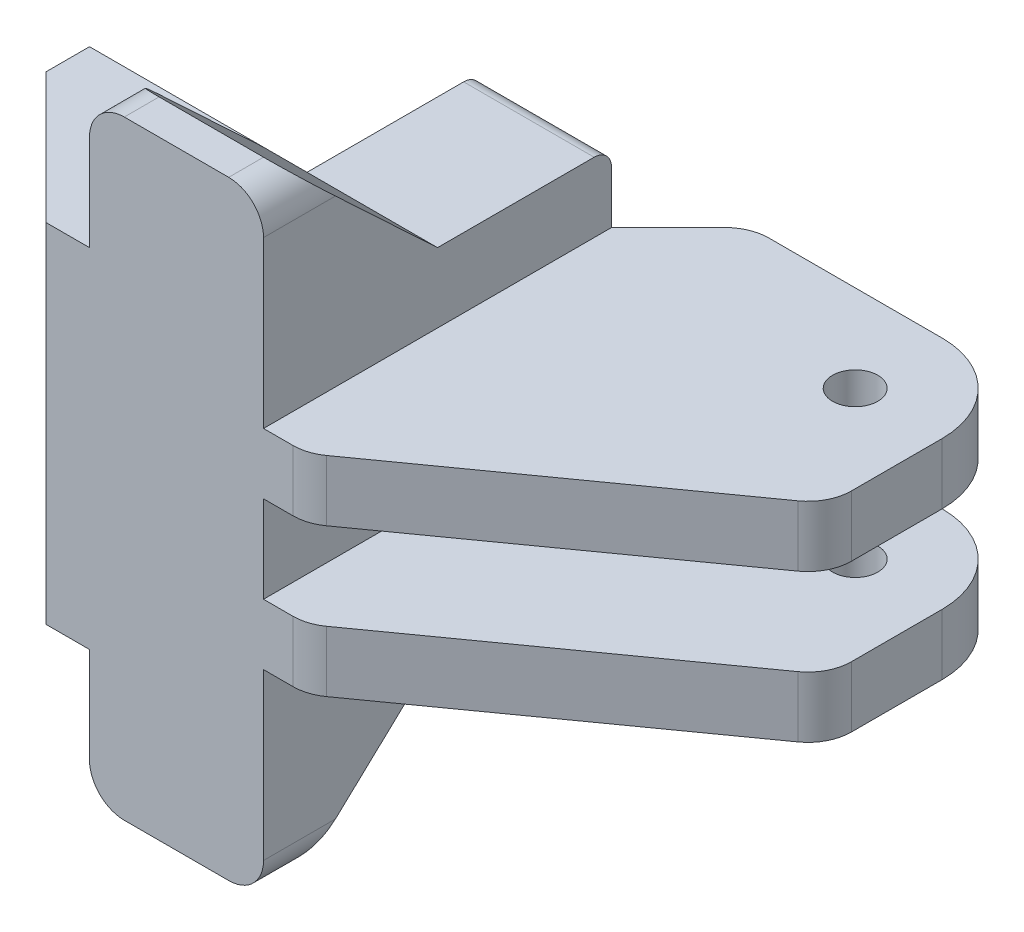
SolidWorks part; units mm, degrees
ref_plane "Front Plane" through (0, 0, 0) normal (0, 0, 1) x (1, 0, 0)
ref_plane "Top Plane" through (0, 0, 0) normal (0, 1, 0) x (1, 0, 0)
ref_plane "Right Plane" through (0, 0, 0) normal (1, 0, 0) x (0, 0, -1)
sketch "Sketch1" plane through (0, 0, 0) normal (0, 1, 0) x (1, 0, 0)
  line L1 (0, 0) -> (40, 0)
  line L2 (0, 0) -> (0, 40)
  line L3 (0, 40) -> (40, 40)
  line L4 (40, 0) -> (40, 40)
extrude "Boss-Extrude1" add sketch "Sketch1" along normal blind 40
sketch "Sketch2" plane through (0, 40, 0) normal (0, 1, 0) x (1, 0, 0)
  line L0 (0, 40) -> (25, 40)
  line L1 (40, 40) -> (0, 40) construction
  line L2 (25, 40) -> (25, 20)
  line L3 (25, 20) -> (0, 20)
  line L4 (0, 40) -> (0, 0) construction
  line L5 (0, 20) -> (0, 40)
extrude "Cut-Extrude1" cut sketch "Sketch2" against normal blind 40
chamfer "Chamfer1" distance 15 angle 45 1 edges at (0, 20, 0)
sketch "Sketch3" plane through (0, 0, 0) normal (0, 0, 1) x (1, 0, 0)
  line L4 (0, 0) -> (0, 40) construction
  line L5 (0, 10) -> (0, 15)
  line L6 (0, 15) -> (15, 15)
  line L7 (15, 15) -> (15, 5)
  line L8 (15, 5) -> (0, 5)
  line L9 (0, 5) -> (0, 10)
  line L11 (0, 30) -> (0, 25)
  line L12 (0, 25) -> (15, 25)
  line L13 (15, 25) -> (15, 35)
  line L14 (15, 35) -> (0, 35)
  line L15 (0, 35) -> (0, 30)
extrude "Cut-Extrude2" cut sketch "Sketch3" against normal blind 15
chamfer "Chamfer2" distance 4 angle 45 4 edges at (15, 5, -7.5) (15, 15, -7.5) (15, 35, -7.5) (15, 25, -7.5)
sketch "Sketch4" plane through (0, 0, -15) normal (0, 0, 1) x (1, 0, 0)
  line L0 (0, 30) -> (8, 30)
  line L1 (0, 35) -> (0, 25) construction
  line L2 (0, 10) -> (8, 10)
  line L3 (0, 15) -> (0, 5) construction
  circle A0 centre (8, 30) radius 2.6
  circle A1 centre (8, 10) radius 2.6
extrude "Cut-Extrude3" cut sketch "Sketch4" against normal blind 17 contours A0 | A1 region at (8, 27.4735, -15) region at (8, 7.4735, -15)
sketch "Sketch5" plane through (0, 0, -40) normal (0, 0, -1) x (-1, 0, 0)
  line L0 (-40, 20) -> (-80, 20)
  line L1 (-40, 40) -> (-40, 0) construction
  line L2 (-80, 32) -> (-80, 25)
  line L3 (-40, 32) -> (-80, 32)
  line L4 (-80, 20) -> (-80, 15)
  line L5 (-80, 15) -> (-40, 15)
  line L6 (-40, 15) -> (-40, 8)
  line L7 (-40, 8) -> (-80, 8)
  line L8 (-80, 8) -> (-80, 15)
  line L9 (-40, 25) -> (-40, 32)
  line L10 (-80, 25) -> (-40, 25)
  line M10 (-40, 40) -> (-40, 0)
  dimension "D1" = 5
extrude "Boss-Extrude2" add sketch "Sketch5" along normal blind 8 and the other way blind 40 contours L8 L7 L5 M10 | L2 L10 L3 M10 region at (60, 28.5, -40) region at (60, 11.5, -40)
chamfer "Chamfer3" distance 35 distance2 25 1 edges at (80, 28.5, 0) first distance on face at (40.625, 20, 0)
chamfer "Chamfer4" distance 25 distance2 35 1 edges at (80, 11.5, 0) first distance on face at (80, 11.5, -24)
chamfer "Chamfer5" distance 8 angle 45 2 edges at (40, 28.5, -48) (40, 11.5, -48)
fillet "Fillet1" radius 10 2 edges at (80, 11.5, -48) (80, 28.5, -48)
fillet "Fillet2" radius 5 6 edges at (45, 28.5, 0) (45, 11.5, 0) (48, 28.5, -48) (48, 11.5, -48) (80, 28.5, -25) (80, 11.5, -25)
sketch "Sketch8" plane through (0, 32, 0) normal (0, 1, 0) x (1, 0, 0)
  circle A0 centre (70, 38) radius 2.6
extrude "Cut-Extrude4" cut sketch "Sketch8" against normal blind 34
sketch "Sketch9" plane through (40, 0, 0) normal (1, 0, 0) x (0, 0, -1)
  line L0 (0, 40) -> (0, 55)
  line L1 (0, 40) -> (20, 40)
  line L2 (0, 40) -> (40, 40) construction
  line L4 (0, 0) -> (0, -15)
  line L5 (0, 0) -> (20, 0)
  line L7 (0, 55) -> (4, 55)
  line L8 (4, 55) -> (20, 40)
  line L9 (0, -15) -> (4, -15)
  line L10 (4, -15) -> (20, 0)
extrude "Boss-Extrude3" add sketch "Sketch9" against normal blind 20
fillet "Fillet3" radius 4 4 edges at (20, -15, -2) (40, -15, -2) (20, 55, -2) (40, 55, -2)
fillet "Fillet4" radius 2 2 edges at (32.5, 0, -40) (32.5, 40, -40)
sketch "Sketch10" plane through (40, 0, 0) normal (1, 0, 0) x (0, 0, -1)
  line L0 (40, 20) -> (36, 20)
  line L1 (40, 25) -> (40, 15) construction
  line L2 (36, 15) -> (36, 25)
  line L3 (40, 25) -> (0, 25) construction
  line L4 (36, 25) -> (22, 25)
  line L5 (22, 25) -> (22, 15)
  line L6 (36, 15) -> (22, 15)
  point P10 (22, 20)
  line M5 (40, 25) -> (0, 25)
  line M7 (0, 15) -> (40, 15)
  dimension "D1" = 4
  dimension "D2" = 14
extrude "Cut-Extrude5" cut sketch "Sketch10" against normal blind 26 contours L5 L2 M5 M7 region at (40, 20, -29)
chamfer "Chamfer6" distance 2 distance2 10 1 edges at (40, 20, -36) first distance on face at (40, 20, -38)
fillet "Fillet5" radius 2 6 edges at (35, 25, -37) (27.5, 25, -36) (35, 15, -37) (27.5, 15, -36) (32.5, 15, -22) (32.5, 25, -22)
